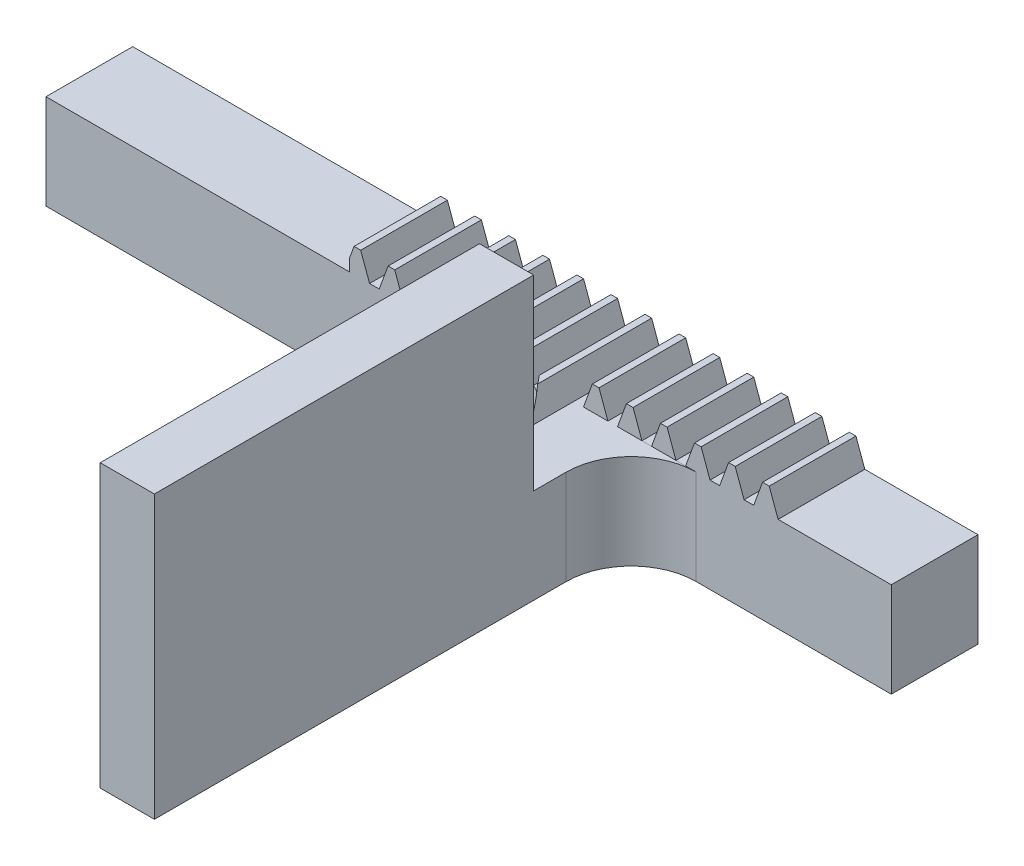
SolidWorks part; units mm, degrees
extrude "Blank" add sketch "BlankSke" against normal blind 4
sketch "BlankSke" plane through (0, 0, 0) normal (0, 0, 1) x (1, 0, 0)
  line L1 (0, 0) -> (20, 0)
  line L2 (0, 0) -> (0, 5.5)
  line L3 (0, 5.5) -> (20, 5.5)
  line L4 (20, 0) -> (20, 5.5)
  dimension "Length" = 20
ref_plane "Plane1" through (0, 0, 0) normal (0, 0, 1) x (1, 0, 0)
ref_plane "Plane2" through (0, 0, 0) normal (0, 1, 0) x (1, 0, 0)
ref_plane "Plane3" through (0, 0, 0) normal (1, 0, 0) x (0, 0, -1)
other "Configuration Table"
sketch "HoldingSke" plane through (0, 0, 0) normal (0, 1, 0) x (1, 0, 0)
  line L0 (0, 0) -> (0.2783, 1.9805)
  line L1 (-15, 0) -> (100, 0) construction
  line L2 (0, 0) -> (-2.1039, 2.3779)
  line L3 (0, 0) -> (-11.863, 4.5341)
  line L4 (0, 0) -> (8.3795, 2.0892)
  line L5 (0, 0) -> (-23.7986, -8.8762)
  line L6 (0, 0) -> (-10.5278, -7.1032)
  line L9 (-71.009, 38.7566) -> (-52.2151, 45.597)
  line L10 (-76.2, 2.8779) -> (-71.2, 2.8779)
  line L11 (0, 0) -> (-2, 0)
  line L12 (-76.2, 101.6) -> (-76.181, 101.6)
  line L13 (24.9733, 27.94) -> (52.9518, 28.4284)
  line L14 (24.9733, 27.94) -> (24.9743, 27.94)
  line L15 (24.9733, 27.94) -> (100.4006, 29.5858)
  circle A0 centre (0, 0) radius 19.05
  circle A1 centre (0, 0) radius 2.5
  circle A2 centre (0, 0) radius 12.7
  dimension "Num_teeth" = 14
  dimension "Width" = 2
  dimension "Length" = 20
  dimension "Pitch_height" = 5
sketch "TooCutSkeIll" plane through (0, 0, 0) normal (0, 0, 1) x (1, 0, 0)
  line L0 (-0.6269, 5.4868) -> (-0.2524, 4.4579)
  line L1 (-0.134, 4.375) -> (0.134, 4.375)
  line L2 (0.2524, 4.4579) -> (0.6269, 5.4868)
  line L3 (20, 5.5) -> (0, 5.5) construction
  line L4 (0, 0) -> (0, 64.897) construction
  line L5 (-13.208, 5) -> (12.954, 5) construction
  line L6 (0, 0) -> (20, 0) construction
  line L7 (0.4497, 5) -> (0.4497, 48.7463) construction
  line L8 (-0.4497, 5) -> (-0.4497, 48.7463) construction
  line L9 (0.6457, 5.5) -> (0.6457, 5.5254)
  line L10 (-0.6457, 5.5) -> (-0.6457, 5.5254)
  line L11 (-0.6457, 5.5254) -> (0.6457, 5.5254)
  arc A0 (0.134, 4.375) -> (0.2524, 4.4579) centre (0.134, 4.501) ccw
  arc A1 (-0.2524, 4.4579) -> (-0.134, 4.375) centre (-0.134, 4.501) ccw
  arc A2 (0.6457, 5.5) -> (0.6269, 5.4868) centre (0.6457, 5.48) ccw
  arc A3 (-0.6269, 5.4868) -> (-0.6457, 5.5) centre (-0.6457, 5.48) ccw
  dimension "Addendum_plus" = 0.5254
  dimension "Pitch_height" = 5
  dimension "Pressure_angle" = 20
  dimension "Gap_width" = 0.8994
  dimension "Dedendum" = 0.625
extrude "ToothCutIll" [suppressed] cut sketch "TooCutSkeIll" against normal through all
sketch "TooCutSkeSim" plane through (0, 0, 0) normal (0, 0, 1) x (1, 0, 0)
  line L0 (0.2222, 4.375) -> (-0.2222, 4.375)
  line L1 (0.6409, 5.5254) -> (0.2222, 4.375)
  line L2 (0, 17.4625) -> (0, 53.467) construction
  line L3 (0.6409, 5.5254) -> (-0.6409, 5.5254)
  line L6 (-0.6409, 5.5254) -> (-0.2222, 4.375)
  line L9 (-0.4497, 5) -> (0.4497, 5) construction
  line L10 (0, 0) -> (20, 0) construction
  line L11 (0.4497, 5) -> (0.4497, 53.467) construction
  line L12 (-0.4497, 5) -> (-0.4497, 53.467) construction
  dimension "Addendum_plus" = 0.5254
  dimension "Pitch_height" = 5
  dimension "Pressure_angle" = 20
  dimension "Gap_width" = 0.8994
  dimension "Dedendum" = 0.625
extrude "ToothCutSim" cut sketch "TooCutSkeSim" against normal through all
pattern_linear "TeethCuts" count 13 spacing 1.5708 along (1, 0, 0) of "ToothCutIll", "ToothCutSim"
sketch "Sketch1" plane through (0, 0, 0) normal (0, 0, 1) x (1, 0, 0)
  line L1 (7, 0) -> (9.5, 0)
  line L2 (7, 0) -> (7, 13)
  line L3 (7, 13) -> (9.5, 13)
  line L4 (9.5, 0) -> (9.5, 13)
  line L5 (7, 0) -> (9.5, 13) construction
  line L6 (7, 13) -> (9.5, 0) construction
  line L8 (0, 0) -> (20, 0) construction
  line L9 (0, 4.375) -> (0, 0) construction
  point P4 (8.25, 6.5)
  dimension "D1" = 2.5
  dimension "D2" = 13
  dimension "D3" = 7
extrude "Boss-Extrude1" add sketch "Sketch1" along normal blind 22
sketch "Sketch3" plane through (0, 0, 0) normal (-1, 0, 0) x (0, 0, 1)
  line L1 (0, 4.375) -> (-4, 4.375)
  line L2 (0, 4.375) -> (0, 0)
  line L3 (0, 0) -> (-4, 0)
  line L4 (-4, 4.375) -> (-4, 0)
  line L5 (0, 4.375) -> (-4, 0) construction
  line L6 (0, 0) -> (-4, 4.375) construction
  point P4 (-2, 2.1875)
extrude "Boss-Extrude3" add sketch "Sketch3" along normal blind 5 and the other way offset from surface (34 mm away) 14 other way up to face at (20, 2.4597, -2)
sketch "Sketch4" plane through (7, 0, 0) normal (-1, 0, 0) x (0, 0, 1)
  line L1 (0, 13) -> (4.5, 13)
  line L2 (0, 13) -> (0, 4.375)
  line L3 (0, 4.375) -> (4.5, 4.375)
  line L4 (4.5, 13) -> (4.5, 4.375)
  line L5 (0, 13) -> (4.5, 4.375) construction
  line L6 (0, 4.375) -> (4.5, 13) construction
  line L7 (-4, 4.375) -> (0, 4.375) construction
  point P4 (2.25, 8.6875)
  dimension "D1" = 4.5
extrude "Cut-Extrude1" cut sketch "Sketch4" against normal through all both and the other way through all
fillet "Fillet1" radius 3 2 edges at (7, 2.1875, 0) (9.5, 2.1875, 0)
mirror "Mirror1" about plane through (34, 0, -4) normal (1, 0, 0) of bodies 106
delete or keep bodies "Body-Delete/Keep 1" type delete bodies bodies 106
equation "' \"Module@HoldingSke\" = 6.35"
equation "' \"Num_teeth@HoldingSke\" = 12"
equation "' \"Ap@HoldingSke\" =  20"
equation "' \"Ap@HoldingSke\" = 20"
equation "' \"Width@HoldingSke\" = 0.25 * 25.4"
equation "' \"Show_teeth@HoldingSke\" = 500"
equation "' \"Backlash@HoldingSke\" = 0.009 * 25.4"
equation "' \"Addendum_fac@HoldingSke\" = 1.0"
equation "' \"Dedendum_fac@HoldingSke\" = 1.25"
equation "' \"Dedendum_add@HoldingSke\" = 0.00005 * 25.4"
equation "' \"Clearance_fac@HoldingSke\" = 0.25"
equation "' \"Pitch_height@HoldingSke\" = 1 * 25.4"
equation "' \"Length@HoldingSke\" = 4.71 * 25.4"
equation "\"Pitch@HoldingSke\" = 1 / \"Module@HoldingSke\""
equation "\"MPH@HoldingSke\" = \"Dedendum_fac@HoldingSke\" / \"Pitch@HoldingSke\" + 2 * \"Dedendum_add@HoldingSke\" + 0.002 * 25.4"
equation "\"MPH@HoldingSke\" = ((sgn( \"MPH@HoldingSke\" - \"Pitch_height@HoldingSke\")+1)*( \"MPH@HoldingSke\" - \"Pitch_height@HoldingSke\"))/2 + \"Pitch_height@HoldingSke\""
equation "\"Blank_height@BlankSke\" = \"Pitch_height@HoldingSke\" + \"Addendum_fac@HoldingSke\"  / \"Pitch@HoldingSke\" "
equation "\"Length@BlankSke\" =  \"Length@HoldingSke\""
equation "\"Pressure_angle@TooCutSkeIll\" = \"Ap@HoldingSke\""
equation "\"Addendum_plus@TooCutSkeIll\" =  \"Addendum_fac@HoldingSke\"  / \"Pitch@HoldingSke\" + 0.001 *25.4"
equation "\"Dedendum@TooCutSkeIll\" = \"Dedendum_fac@HoldingSke\"  / \"Pitch@HoldingSke\""
equation "\"Pitch_height@TooCutSkeIll\" =  \"MPH@HoldingSke\""
equation "\"Gap_width@TooCutSkeIll\" = 3.14159265 / 2 / \"Pitch@HoldingSke\" + 6 * \"Backlash@HoldingSke\""
equation "\"Pressure_angle@TooCutSkeSim\" = \"Ap@HoldingSke\""
equation "\"Addendum_plus@TooCutSkeSim\" =  \"Addendum_fac@HoldingSke\"  / \"Pitch@HoldingSke\" + 0.001 * 25.4"
equation "\"Dedendum@TooCutSkeSim\" = \"Dedendum_fac@HoldingSke\"  / \"Pitch@HoldingSke\""
equation "\"Pitch_height@TooCutSkeSim\" =  \"MPH@HoldingSke\""
equation "\"Gap_width@TooCutSkeSim\" = 3.14159265 / 2 / \"Pitch@HoldingSke\" + 6 * \"Backlash@HoldingSke\""
equation "\"Root_fillet@TooCutSkeIll\" = \"Clearance_fac@HoldingSke\" / \"Pitch@HoldingSke\" + \"Dedendum_add@HoldingSke\""
equation "\"Break_rad@TooCutSkeIll\" = 0.02 / \"Pitch@HoldingSke\" * 2"
equation "\"Linear_pitch@TeethCuts\" = 3.14159265 / \"Pitch@HoldingSke\""
equation "\"Num_teeth@HoldingSke\" = int( ( \"Length@HoldingSke\" + 0 ) / (3.14159265 / \"Pitch@HoldingSke\")) + 0.9999  + 1"
equation " \"Num_teeth@TeethCuts\" = int( \"Show_teeth@HoldingSke\" ) + 1"
equation " \"Num_teeth@TeethCuts\" = ((sgn( \"Num_teeth@TeethCuts\" - \"Num_teeth@HoldingSke\" )-1)*( \"Num_teeth@TeethCuts\" - \"Num_teeth@HoldingSke\" ))/-2+ \"Num_teeth@HoldingSke\""
equation " \"Num_teeth@TeethCuts\" = ((sgn( \"Num_teeth@TeethCuts\" - 2.0)+1)*( \"Num_teeth@TeethCuts\" - 2.0))/2 +2.0"
